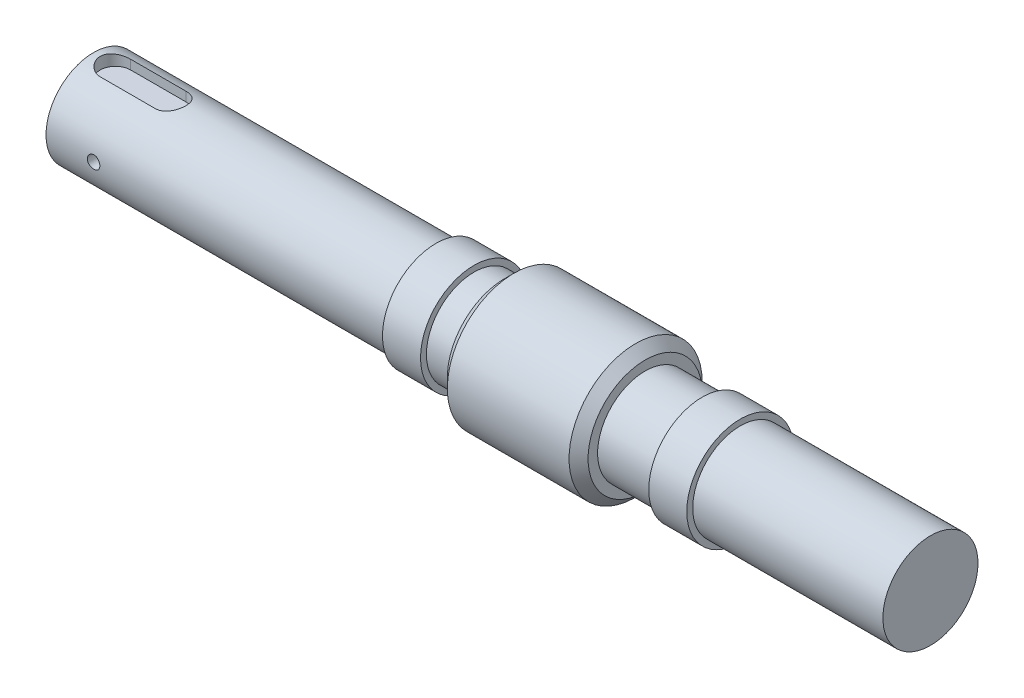
SolidWorks part; units mm, degrees
ref_plane "Frontal" through (0, 0, 0) normal (0, 0, 1) x (1, 0, 0)
ref_plane "Superior" through (0, 0, 0) normal (0, 1, 0) x (1, 0, 0)
ref_plane "Izquierda" through (0, 0, 0) normal (1, 0, 0) x (0, 0, -1)
sketch "Croquis1" plane through (0, 0, 0) normal (1, 0, 0) x (0, 0, -1)
  circle A0 centre (0, 0) radius 35
  dimension "D1" = 70
extrude "Saliente-Extruir1" add sketch "Croquis1" along normal mid plane 74
ref_plane "Plano1" through (7, 0, 0) normal (-1, 0, 0) x (0, 0, 1)
chamfer "Chaflán1" distance 5 angle 45 2 edges at (37, 0, -35) (-37, 0, -35)
sketch "Croquis2" plane through (-37, 0, 0) normal (-1, 0, 0) x (0, 0, 1)
  circle A0 centre (0, 0) radius 25
  dimension "D1" = 50
extrude "Saliente-Extruir2" add sketch "Croquis2" along normal blind 16
sketch "Croquis3" plane through (-53, 0, 0) normal (-1, 0, 0) x (0, 0, 1)
  circle A0 centre (0, 0) radius 28.1
  dimension "D1" = 56.2
extrude "Saliente-Extruir3" add sketch "Croquis3" along normal blind 120
chamfer "Chaflán2" [suppressed] distance 2.5 angle 45
sketch "Croquis4" plane through (37, 0, 0) normal (1, 0, 0) x (0, 0, -1)
  circle A0 centre (0, 0) radius 25
  dimension "D1" = 50
extrude "Saliente-Extruir4" add sketch "Croquis4" along normal blind 30
sketch "Croquis5" plane through (67, 0, 0) normal (1, 0, 0) x (0, 0, -1)
  circle A0 centre (0, 0) radius 28.1
  dimension "D1" = 56.2
extrude "Saliente-Extruir5" add sketch "Croquis5" along normal blind 120
chamfer "Chaflán3" [suppressed] distance 2.5 angle 45
sketch "Croquis6" plane through (-173, 0, 0) normal (-1, 0, 0) x (0, 0, 1)
  circle A0 centre (0, 0) radius 25
  circle A1 centre (0, 0) radius 28.1
extrude "Cortar-Extruir1" cut sketch "Croquis6" against normal blind 100
sketch "Croquis8" plane through (187, 0, 0) normal (1, 0, 0) x (0, 0, -1)
  circle A0 centre (0, 0) radius 25
  circle A1 centre (0, 0) radius 28.1
extrude "Cortar-Extruir2" cut sketch "Croquis8" against normal blind 100
sketch "Croquis9" plane through (-173, 0, 0) normal (-1, 0, 0) x (0, 0, 1)
  circle A0 centre (0, 0) radius 25
  dimension "D1" = 50
extrude "Saliente-Extruir6" add sketch "Croquis9" along normal blind 80
sketch "Croquis10" plane through (0, 0, 0) normal (0, 1, 0) x (1, 0, 0)
  line L0 (-253, 0) -> (-66.718, 0) construction
  line L1 (-253, 25) -> (-253, -25) construction
  line L2 (-241.5, 0) -> (-212.5, 0) construction
  line L3 (-241.5, 8) -> (-212.5, 8)
  line L4 (-241.5, -8) -> (-212.5, -8)
  arc A0 (-241.5, 8) -> (-241.5, -8) centre (-241.5, 0) ccw
  arc A1 (-212.5, -8) -> (-212.5, 8) centre (-212.5, 0) ccw
  point P7 (-227, 0)
  point P12 (-249.5, 0)
  point P13 (-204.5, 0)
  dimension "D1" = 45
  dimension "D2" = 16
  dimension "D3" = 26
extrude "Cortar-Extruir3" cut sketch "Croquis10" along normal blind 6.2 from offset 18.8
hole_wizard "Taladro de margen para M61" positions "Croquis3D2" profile "Croquis12" hole size "M6" standard "DIN"
sketch3d "Croquis3D2"
  line L0 (-253, 0, 0) -> (-253, 48.809, 0) construction
  line L1 (-73, 0, 0) -> (-253, 0, 0) construction
  line L3 (-253, 0, 0) -> (-253, -25, 0) construction
  line L5 (-253, 0, 0) -> (-253, 0, 25) construction
  line L6 (-253, 0, 25) -> (-198.2724, 0, 25) construction
  line L8 (-253, -25, 0) -> (-213.979, -25, 0) construction
  circle A0 centre (-253, 0, 0) radius 25 construction
  point P17 (-278, 0, 0)
  point P35 (-228, 0, 25)
  point P37 (-228, -25, 0)
  dimension "D1" = 25
  dimension "D2" = 25
sketch "Croquis12" plane through (-228, -25, 0) normal (1, 0, 0) x (0, 0, -1)
  line L0 (0, 0) -> (0, 18.9828)
  line L1 (0, 18.9828) -> (3.3, 17)
  line L2 (3.3, 17) -> (3.3, 0)
  line L5 (3.3, 0) -> (0, 0)
  line L10 (0, 18.9828) -> (-3.3, 17) construction
  line L11 (0, -6.35) -> (0, 107.95) construction
  dimension "Diámetro de taladro" = 6.6
  dimension "Profundidad de taladro" = 17
  dimension "Ángulo de perforador" = 118
